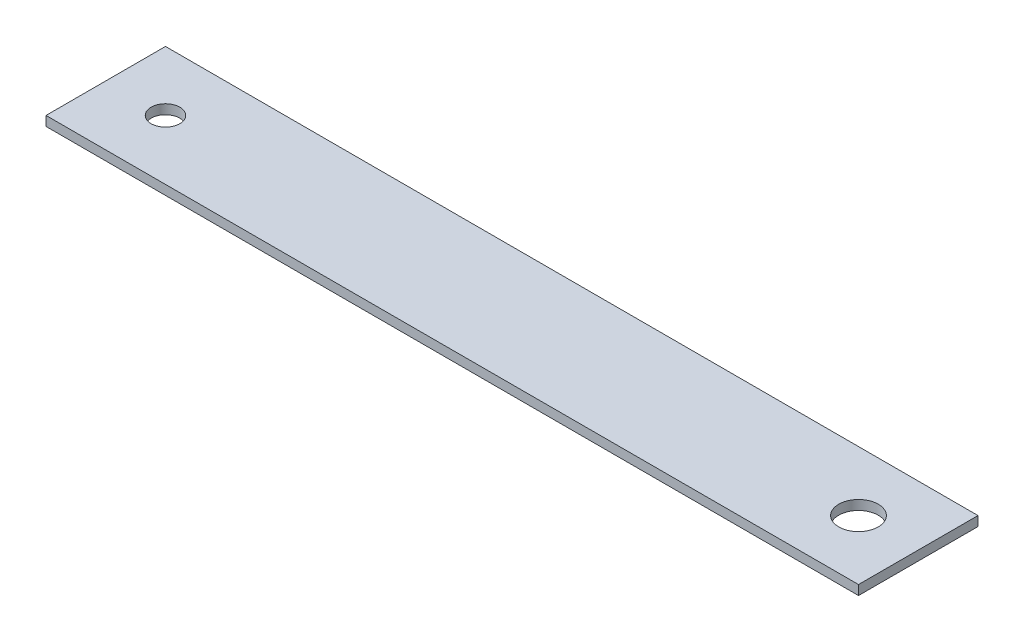
SolidWorks part; units mm, degrees
ref_plane "Front Plane" through (0, 0, 0) normal (0, 0, 1) x (1, 0, 0)
ref_plane "Top Plane" through (0, 0, 0) normal (0, 1, 0) x (1, 0, 0)
ref_plane "Right Plane" through (0, 0, 0) normal (1, 0, 0) x (0, 0, -1)
sketch "Sketch1" plane through (0, 0, 0) normal (0, 1, 0) x (1, 0, 0)
  line L1 (-85, 12.5) -> (85, 12.5)
  line L2 (-85, 12.5) -> (-85, -12.5)
  line L3 (-85, -12.5) -> (85, -12.5)
  line L4 (85, 12.5) -> (85, -12.5)
  line L5 (-85, 12.5) -> (85, -12.5) construction
  line L6 (-85, -12.5) -> (85, 12.5) construction
  circle A0 centre (-10.6801, 3.3392) radius 4.5
  circle A1 centre (-10.6585, -3.6607) radius 14
  circle A2 centre (-28.1585, -4.7634) radius 2
  circle A3 centre (6.8415, -4.7634) radius 2
  circle A4 centre (72.5, 0) radius 4.125
  point P0 (0, 0)
  point P17 (85, 0)
  dimension "D3" = 12.5
  dimension "D4" = 4
  dimension "D5" = 4
  dimension "D6" = 8.25
  dimension "D1" = 25
  dimension "D2" = 170
extrude "Boss-Extrude1" add sketch "Sketch1" along normal blind 2 contours A1 L3 L4 L1 L2 A4 A3 A2 | L3 A1 A0 | A0 region at (0, 0, -10.7817) region at (-10.6556, 0, 2.8007)
sketch "Sketch2" plane through (0, 2, 0) normal (0, 1, 0) x (1, 0, 0)
  line L0 (-85, 12.5) -> (-85, -12.5) construction
  circle A0 centre (-72.5, 0) radius 3
  circle A1 centre (-72.5, 0) radius 20 construction
  circle A2 centre (-42.5, 0) radius 10 construction
  dimension "D1" = 6
  dimension "D2" = 12.5
extrude "Cut-Extrude1" cut sketch "Sketch2" against normal through all
extrude "Boss-Extrude2" add sketch "Sketch1<3>" along normal blind 2 contours A2 | A3 region at (-28.1585, 0, 4.7634) region at (6.8415, 0, 4.7634)
sketch "Sketch1<3>" plane through (0, 0, 0) normal (0, 1, 0) x (1, 0, 0) same geometry as "Sketch1"
